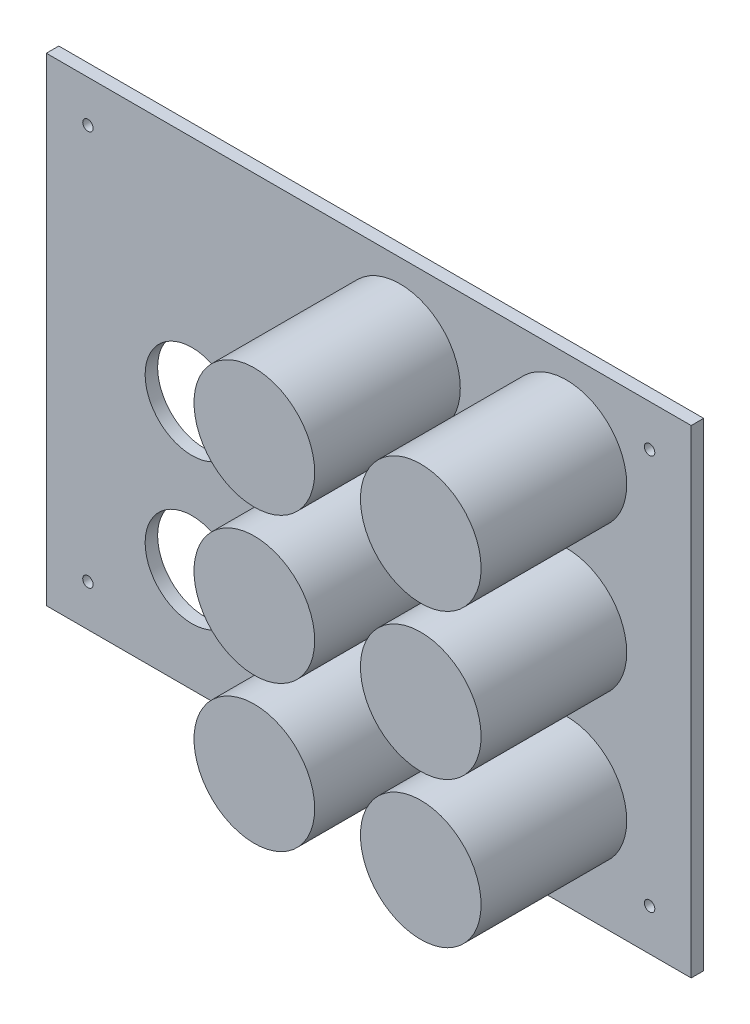
SolidWorks part; units mm, degrees
ref_plane "Plano frontal" through (0, 0, 0) normal (0, 0, 1) x (1, 0, 0)
ref_plane "Plano superior" through (0, 0, 0) normal (0, 1, 0) x (1, 0, 0)
ref_plane "Plano direito" through (0, 0, 0) normal (1, 0, 0) x (0, 0, -1)
sketch "Esboço1" plane through (0, 0, 0) normal (0, 0, 1) x (1, 0, 0)
  line L1 (-77.5, 57.5) -> (77.5, 57.5)
  line L2 (-77.5, 57.5) -> (-77.5, -57.5)
  line L3 (-77.5, -57.5) -> (77.5, -57.5)
  line L4 (77.5, 57.5) -> (77.5, -57.5)
  line L5 (-77.5, 57.5) -> (77.5, -57.5) construction
  line L6 (-77.5, -57.5) -> (77.5, 57.5) construction
  point P0 (0, 0)
  dimension "D1" = 115
  dimension "D2" = 155
extrude "Ressalto-extrusão1" add sketch "Esboço1" along normal blind 3
sketch "Esboço11" plane through (0, 0, 0) normal (0, 0, -1) x (-1, 0, 0)
  line L0 (-77.5, 57.5) -> (77.5, 57.5) construction
  line L2 (-77.5, -57.5) -> (-77.5, 57.5) construction
  circle A0 centre (-7.5, -32.5) radius 12.5
  circle A1 centre (-47.5, -32.5) radius 12.5
  circle A2 centre (-47.5, 2.5) radius 12.5
  circle A3 centre (-47.5, 37.5) radius 12.5
  circle A4 centre (-7.5, 37.5) radius 12.5
  circle A5 centre (-7.5, 2.5) radius 12.5
  point P14 (0, 0)
  point P15 (0, 0)
  point P16 (0, 0)
  dimension "D1" = 25
  dimension "D2" = 20
  dimension "D3" = 20
  dimension "D4" = 35
  dimension "D5" = 35
  dimension "D6" = 35
  dimension "D7" = 30
  dimension "D8" = 30
  dimension "D9" = 40
  dimension "D10" = 35
  dimension "D11" = 40
  dimension "D12" = 40
  dimension "D13" = 30
sketch "Esboço12" plane through (0, 0, 3) normal (0, 0, 1) x (1, 0, 0)
  circle A0 centre (7.5, 37.5) radius 14.5
  circle A1 centre (7.5, 37.5) radius 12.5 construction
  circle A2 centre (47.5, 37.5) radius 14.5
  circle A3 centre (7.5, 2.5) radius 14.5
  circle A4 centre (47.5, 2.5) radius 14.5
  circle A5 centre (47.5, -32.5) radius 14.5
  circle A6 centre (7.5, -32.5) radius 14.5
  dimension "D1" = 2
extrude "Ressalto-extrusão14" add sketch "Esboço12" along normal blind 35 separate body contours A3 | A4 | A0 | A2 | A5 | A6
extrude "Corte-extrusão8" cut sketch "Esboço11" against normal blind 35 contours A3
extrude "Corte-extrusão9" cut sketch "Esboço11<5>" against normal blind 35 contours A1 | A0 | A2 | A4 | A5
sketch "Esboço11<5>" plane through (0, 0, 0) normal (0, 0, -1) x (-1, 0, 0) same geometry as "Esboço11"
sketch "Esboço13" plane through (0, 0, 0) normal (0, 0, -1) x (-1, 0, 0)
  line L0 (77.5, 57.5) -> (77.5, -57.5) construction
  line L1 (77.5, -57.5) -> (-77.5, -57.5) construction
  circle A0 centre (42.5, -32.5) radius 11.25
  circle A1 centre (42.5, 2.5) radius 11.25
  point P2 (0, 0)
  point P3 (0, 0)
  dimension "D1" = 22.5
  dimension "D2" = 35
  dimension "D3" = 25
  dimension "D4" = 35
  dimension "D5" = 35
sketch "Esboço14" plane through (0, 0, 0) normal (0, 0, -1) x (-1, 0, 0)
  line L0 (77.5, -57.5) -> (-77.5, -57.5) construction
  line L1 (77.5, 57.5) -> (77.5, -57.5) construction
  line L2 (-77.5, 57.5) -> (77.5, 57.5) construction
  line L3 (-77.5, -57.5) -> (-77.5, 57.5) construction
  circle A0 centre (67.5, -47.5) radius 2.5
  circle A1 centre (67.5, 47.5) radius 2.5
  circle A2 centre (-67.5, 47.5) radius 2.5
  circle A3 centre (-67.5, -47.5) radius 2.5
  point P8 (0, 0)
  point P9 (0, 0)
  point P16 (0, 0)
  point P18 (77.5, 47.4136)
  point P20 (0, 0)
  dimension "D1" = 5
  dimension "D2" = 10
  dimension "D3" = 10
  dimension "D4" = 10
  dimension "D5" = 10
  dimension "D6" = 10
  dimension "D7" = 10
  dimension "D8" = 10
  dimension "D9" = 10
hole_wizard "Rebaixo para parafuso de máquina com cabeça panela de #01" positions "3DSketch1" profile "Esboço15" counterbore size "#0" standard "Ansi Inch" end condition through all
sketch3d "3DSketch1"
  point P0 (-67.5, -47.5, 0)
  point P3 (-67.5, 47.5, 0)
  point P6 (67.5, 47.5, 0)
  point P9 (67.5, -47.5, 0)
sketch "Esboço15" plane through (-67.5, -47.5, 0) normal (1, 0, 0) x (0, 1, 0)
  line L0 (0, 0) -> (0, 38)
  line L1 (0, 38) -> (1.25, 38)
  line L3 (1.25, 38) -> (1.25, 1.1176)
  line L4 (1.7856, 1.1176) -> (1.25, 1.1176)
  line L5 (1.7856, 1.1176) -> (1.7856, 0.8218)
  line L6 (1.7856, 0.8218) -> (2.5, 0)
  line L7 (2.5, 0) -> (0, 0)
  line L8 (-1.7856, 0.8218) -> (-2.5, 0) construction
  line L11 (0, -6.35) -> (0, 107.95) construction
  dimension "Thru Hole Dia." = 2.5
  dimension "Thru Hole Depth" = 38
  dimension "C'Bore Dia." = 3.5712
  dimension "C'Bore Depth" = 1.1176
  dimension "Near C'Sink Dia." = 5
  dimension "Near C'Sink Angle" = 82
extrude "Botões" cut sketch "Esboço13" against normal up to next (3 mm away)
sketch "6" plane through (0, 0, 0) normal (0, 0, -1) x (-1, 0, 0)
  circle A0 centre (-27.5, 34.5) radius 1
  circle A1 centre (-27.5, 37.5) radius 1
  circle A2 centre (-27.5, 40.5) radius 1
  circle A3 centre (-24.5, 40.5) radius 1
  circle A4 centre (-33, 34.5) radius 1
  circle A5 centre (-30.5, 34.5) radius 1
  circle A6 centre (-47.5, 37.5) radius 12.5 construction
  circle A7 centre (-30.5, 37.5) radius 1
  point P12 (-36.4087, 45.4216)
  point P13 (-36.4087, 45.4216)
  point P14 (-24.1066, 12.7231)
  point P15 (-43.1231, 2.2984)
  point P18 (-43.1231, 2.2984)
  point P19 (-43.1231, 2.2984)
  point P20 (-43.1231, 2.2984)
  point P24 (0, 0)
  point P25 (0, 0)
  dimension "D4" = 20
  dimension "D6" = 3
  dimension "D9" = 3
  dimension "D12" = 2
  dimension "D13" = 3
  dimension "D1" = 3
  dimension "D2" = 3
  dimension "D3" = 3
  dimension "D5" = 3
  dimension "D7" = 3
  dimension "D8" = 3
  dimension "D10" = 2.5
  dimension "D11" = 0
  dimension "D14" = 3
sketch "4" plane through (0, 0, 0) normal (0, 0, -1) x (-1, 0, 0)
  circle A0 centre (-27.5, -35.5) radius 1
  circle A1 centre (-27.5, -32.5) radius 1
  circle A2 centre (-27.5, -29.5) radius 1
  circle A3 centre (-24.5, -29.5) radius 1
  circle A4 centre (-33, -35.5) radius 1
  circle A5 centre (-30.5, -35.5) radius 1
  circle A6 centre (-47.5, -32.5) radius 12.5 construction
  circle A7 centre (-33, -32.5) radius 1
  point P8 (0, 0)
  point P12 (-37.244, -24.5734)
  point P13 (-37.244, -24.5734)
  point P14 (-24.9419, -57.2718)
  point P15 (-43.9584, -67.6965)
  point P18 (-43.9584, -67.6965)
  point P19 (-43.9584, -67.6965)
  point P20 (-43.9584, -67.6965)
  point P24 (-0.8353, -69.995)
  point P25 (-0.8353, -69.995)
  dimension "D4" = 3
  dimension "D6" = 3
  dimension "D9" = 0
  dimension "D12" = 2
  dimension "D13" = 0
  dimension "D14" = 0
  dimension "D1" = 3
  dimension "D2" = 3
  dimension "D3" = 3
  dimension "D5" = 3
  dimension "D7" = 3
  dimension "D8" = 3
  dimension "D10" = 2.5
  dimension "D11" = 20
sketch "Esboço28" plane through (0, 0, 0) normal (0, 0, -1) x (-1, 0, 0)
  circle A0 centre (12.5, -0.5) radius 1
  circle A1 centre (12.5, 2.5) radius 1
  circle A2 centre (12.5, 5.5) radius 1
  circle A3 centre (15.5, 5.5) radius 1
  circle A4 centre (9.5, 2.5) radius 1
  circle A5 centre (9.5, -0.5) radius 1
  point P8 (0, 0)
  point P12 (0.5979, 9.3372)
  point P13 (0.5979, 9.3372)
  point P14 (12.9, -23.3613)
  point P15 (-6.1165, -33.7859)
  point P18 (-6.1165, -33.7859)
  point P19 (-6.1165, -33.7859)
  point P20 (-6.1165, -33.7859)
  point P24 (37.0066, -36.0844)
  point P25 (37.0066, -36.0844)
  dimension "D4" = 20
  dimension "D6" = 3
  dimension "D9" = 3
  dimension "D12" = 2
  dimension "D1" = 3
  dimension "D2" = 3
  dimension "D3" = 3
  dimension "D5" = 3
  dimension "D7" = 3
  dimension "D8" = 3
  dimension "D10" = 3
  dimension "D11" = 0
sketch "Esboço29" plane through (0, 0, 0) normal (0, 0, -1) x (-1, 0, 0)
  circle A0 centre (12.5, -35.5) radius 1
  circle A1 centre (12.5, -32.5) radius 1
  circle A2 centre (12.5, -29.5) radius 1
  circle A3 centre (15.5, -29.5) radius 1
  circle A5 centre (9.5, -35.5) radius 1
  point P12 (2.4719, -29.7395)
  point P13 (2.4719, -29.7395)
  point P14 (14.774, -62.4379)
  point P15 (-4.2425, -72.8626)
  point P18 (-4.2425, -72.8626)
  point P19 (-4.2425, -72.8626)
  point P20 (-4.2425, -72.8626)
  point P24 (38.8806, -75.161)
  point P25 (38.8806, -75.161)
  dimension "D4" = 20
  dimension "D6" = 3
  dimension "D9" = 3
  dimension "D12" = 2
  dimension "D1" = 3
  dimension "D2" = 3
  dimension "D3" = 3
  dimension "D5" = 3
  dimension "D8" = 3
  dimension "D11" = 0
extrude "Pino 1" add sketch "Esboço29" along normal blind 1.5
extrude "Pino 2" add sketch "Esboço28" along normal blind 1.5
sketch "3" plane through (0, 0, 0) normal (0, 0, -1) x (-1, 0, 0)
  circle A0 centre (12.5, 34.5) radius 1
  circle A1 centre (12.5, 37.5) radius 1
  circle A2 centre (12.5, 40.5) radius 1
  circle A3 centre (15.5, 40.5) radius 1
  circle A4 centre (7, 34.5) radius 1
  circle A5 centre (9.5, 34.5) radius 1
  circle A7 centre (-7.5, 37.5) radius 12.5 construction
  point P12 (6.7144, 43.1232)
  point P13 (6.7144, 43.1232)
  point P14 (19.0165, 10.4247)
  point P15 (0, 0)
  point P18 (0, 0)
  point P19 (0, 0)
  point P20 (0, 0)
  dimension "D4" = 20
  dimension "D6" = 3
  dimension "D9" = 3
  dimension "D12" = 2
  dimension "D1" = 3
  dimension "D2" = 3
  dimension "D3" = 3
  dimension "D5" = 3
  dimension "D7" = 3
  dimension "D8" = 3
  dimension "D10" = 2.5
  dimension "D11" = 0
extrude "Pino 3" add sketch "3" along normal blind 1.5
extrude "Pino 4" add sketch "4" along normal blind 1.5
sketch "5" plane through (0, 0, 0) normal (0, 0, -1) x (-1, 0, 0)
  circle A0 centre (-27.5, -0.5) radius 1
  circle A1 centre (-27.5, 2.5) radius 1
  circle A2 centre (-27.5, 5.5) radius 1
  circle A3 centre (-24.5, 5.5) radius 1
  circle A5 centre (-30.5, -0.5) radius 1
  circle A7 centre (-33, 2.5) radius 1
  point P8 (-0.6707, 30.5988)
  point P12 (-37.9147, 6.0254)
  point P13 (-37.9147, 6.0254)
  point P14 (-25.6126, -26.6731)
  point P15 (-44.6291, -37.0978)
  point P18 (-44.6291, -37.0978)
  point P19 (-44.6291, -37.0978)
  point P20 (-44.6291, -37.0978)
  point P24 (-1.506, -39.3962)
  point P25 (-1.506, -39.3962)
  dimension "D4" = 2.5
  dimension "D6" = 3
  dimension "D9" = 20
  dimension "D12" = 2
  dimension "D13" = 0
  dimension "D1" = 3
  dimension "D2" = 3
  dimension "D3" = 3
  dimension "D5" = 3
  dimension "D7" = 3
  dimension "D8" = 3
  dimension "D10" = 0
extrude "Pino 5" add sketch "5" along normal blind 1.5
extrude "Pino 6" add sketch "6" along normal blind 1.5
